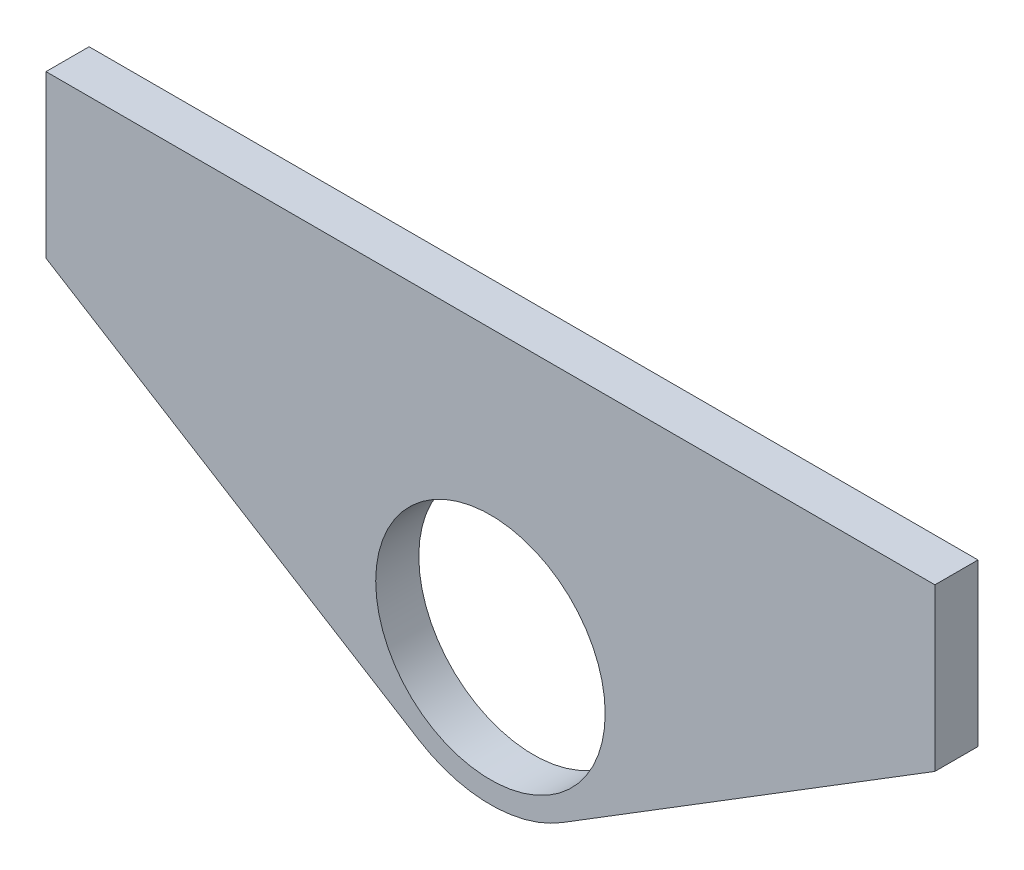
SolidWorks part; units mm, degrees
material "AISI 1020"
ref_plane "Спереди" through (0, 0, 0) normal (0, 0, 1) x (1, 0, 0)
ref_plane "Сверху" through (0, 0, 0) normal (0, 1, 0) x (1, 0, 0)
ref_plane "Справа" through (0, 0, 0) normal (1, 0, 0) x (0, 0, -1)
sketch "Эскиз1" plane through (0, 0, 0) normal (0, 0, 1) x (1, 0, 0)
  line L0 (0, 0) -> (-34.5944, -21.407)
  line L1 (-41.2508, -10.65) -> (-41.2508, 45.5) construction
  line L2 (0, 45.5) -> (-200, 45.5) construction
  line L3 (-82.5017, 0) -> (-47.9073, -21.407)
  line L4 (-82.5017, 0) -> (-82.5017, 15)
  line L5 (-82.5017, 15) -> (0, 15)
  line L6 (0, 4) -> (0, 45.5) construction
  line L7 (0, 15) -> (0, 0)
  circle A0 centre (-41.2508, -10.65) radius 10.65 construction
  circle A1 centre (-41.2508, -10.65) radius 10.65
  arc A2 (-47.9073, -21.407) -> (-34.5944, -21.407) centre (-41.2508, -10.65) ccw
  circle A3 centre (-41.2508, -10.65) radius 12.65 construction
  dimension "D2" = 15
  dimension "D1" = 2
base flange "Базовая кромка1" sketch "Эскиз1" thickness 4 reverse thickness direction no parameters "D1"=0.74
sketch "Сгиб-Линии1" [suppressed] plane through (0, 0, 0) normal (0, 1, 0) x (1, 0, 0)
sketch "Граничная рамка1" [suppressed] plane through (0, 0, 0) normal (0, 1, 0) x (1, 0, 0)
sheet metal parameters "Листовой металл3" thickness 4 parameters "D1"=0.74
flat pattern "Развертка3" [suppressed]
sketch "Сгиб-Линии2" plane through (0, 0, 0) normal (0, 1, 0) x (1, 0, 0)
sketch3d "Граничная рамка2" [suppressed]
  line L0 (-41.2508, -12.65, 0) -> (41.2508, -12.65, 0) construction
  line L1 (-41.2508, 25.65, 0) -> (41.2508, 25.65, 0) construction
  line L2 (-41.2508, -12.65, 0) -> (-41.2508, 25.65, 0) construction
  line L3 (41.2508, -12.65, 0) -> (41.2508, 25.65, 0) construction
